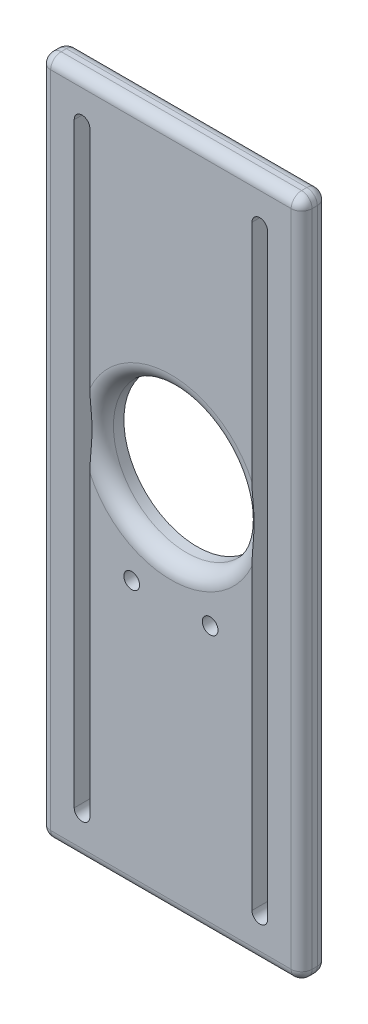
SolidWorks part; units mm, degrees
ref_plane "Front Plane" through (0, 0, 0) normal (0, 0, 1) x (1, 0, 0)
ref_plane "Top Plane" through (0, 0, 0) normal (0, 1, 0) x (1, 0, 0)
ref_plane "Right Plane" through (0, 0, 0) normal (1, 0, 0) x (0, 0, -1)
sketch "Base" plane through (0, 0, 0) normal (0, 0, 1) x (1, 0, 0)
  line L0 (43.6224, 52.8458) -> (43.6224, 40.7373) construction
  line L1 (3.1224, 117.8458) -> (53.1224, 117.8458)
  line L2 (3.1224, 117.8458) -> (3.1224, -12.1542)
  line L3 (3.1224, -12.1542) -> (53.1224, -12.1542)
  line L4 (53.1224, 117.8458) -> (53.1224, -12.1542)
  line L8 (45.1224, 109.8458) -> (45.1224, -4.1542) construction
  line L9 (3.1224, 40.7373) -> (3.1224, 52.8458) construction
  line L12 (46.6224, 109.8458) -> (46.6224, -4.1542)
  line L13 (43.6224, 109.8458) -> (43.6224, -4.1542)
  line L14 (11.1224, 109.8458) -> (11.1224, -4.1542) construction
  line L15 (12.6224, 109.8458) -> (12.6224, -4.1542)
  line L16 (9.6224, 109.8458) -> (9.6224, -4.1542)
  circle A4 centre (28.1224, 59.8458) radius 14
  arc A5 (46.6224, 109.8458) -> (43.6224, 109.8458) centre (45.1224, 109.8458) ccw
  arc A6 (43.6224, -4.1542) -> (46.6224, -4.1542) centre (45.1224, -4.1542) ccw
  arc A7 (12.6224, 109.8458) -> (9.6224, 109.8458) centre (11.1224, 109.8458) ccw
  arc A8 (9.6224, -4.1542) -> (12.6224, -4.1542) centre (11.1224, -4.1542) ccw
  point P6 (28.1224, 117.8458)
  point P13 (45.1224, 52.8458)
  point P31 (11.1224, 52.8458)
  dimension "D5" = 28
  dimension "D6" = 17
  dimension "D4" = 8
  dimension "D11" = 114
  dimension "D2" = 8
  dimension "D7" = 130
  dimension "D8" = 50
  dimension "D9" = 17
  dimension "D10" = 50
  dimension "D12" = 3
extrude "Boss-Extrude1" add sketch "Base" along normal blind 5
sketch "Sketch4" plane through (0, 0, 5) normal (0, 0, 1) x (1, 0, 0)
  line L0 (28.1224, 45.8458) -> (53.1224, 45.8458) construction
  line L1 (53.1224, -12.1542) -> (53.1224, 117.8458) construction
  line L2 (53.1224, 45.8458) -> (53.1224, 32.1458) construction
  line L3 (53.1224, 32.1458) -> (3.1224, 32.1458) construction
  line L4 (3.1224, 117.8458) -> (3.1224, -12.1542) construction
  line L5 (3.1224, 32.1458) -> (3.1224, 45.8458) construction
  line L6 (3.1224, 45.8458) -> (28.1224, 45.8458) construction
  line L7 (3.1224, 38.9958) -> (20.6224, 38.9958) construction
  line L8 (53.1224, 38.9958) -> (35.6224, 38.9958) construction
  circle A0 centre (28.1224, 59.8458) radius 14 construction
  circle A1 centre (20.6224, 38.9958) radius 1.5
  circle A2 centre (35.6224, 38.9958) radius 1.5
  dimension "D1" = 17.5
  dimension "D4" = 3
  dimension "D2" = 15
  dimension "D3" = 13.7
fillet "Fillet3" radius 2 12 edges at (28.1224, -12.1542, 5) (28.1224, -12.1542, 0) (28.1224, 117.8458, 5) (28.1224, 117.8458, 0) (3.1224, 117.8458, 2.5) (3.1224, 52.8458, 5) (3.1224, -12.1542, 2.5) (3.1224, 52.8458, 0) (53.1224, -12.1542, 2.5) (53.1224, 52.8458, 5) (53.1224, 117.8458, 2.5) (53.1224, 52.8458, 0)
fillet "Fillet5" radius 3 1 edges at (42.1224, 59.8458, 5)
extrude "Cut-Extrude1" cut sketch "Sketch4" against normal blind 5
sketch "Sketch5" plane through (0, 0, 0) normal (0, 0, -1) x (-1, 0, 0)
  circle A0 centre (-20.6224, 38.9958) radius 2.5
  circle A1 centre (-35.6224, 38.9958) radius 2.5
  dimension "D1" = 5
extrude "Cut-Extrude2" cut sketch "Sketch5" against normal blind 2
